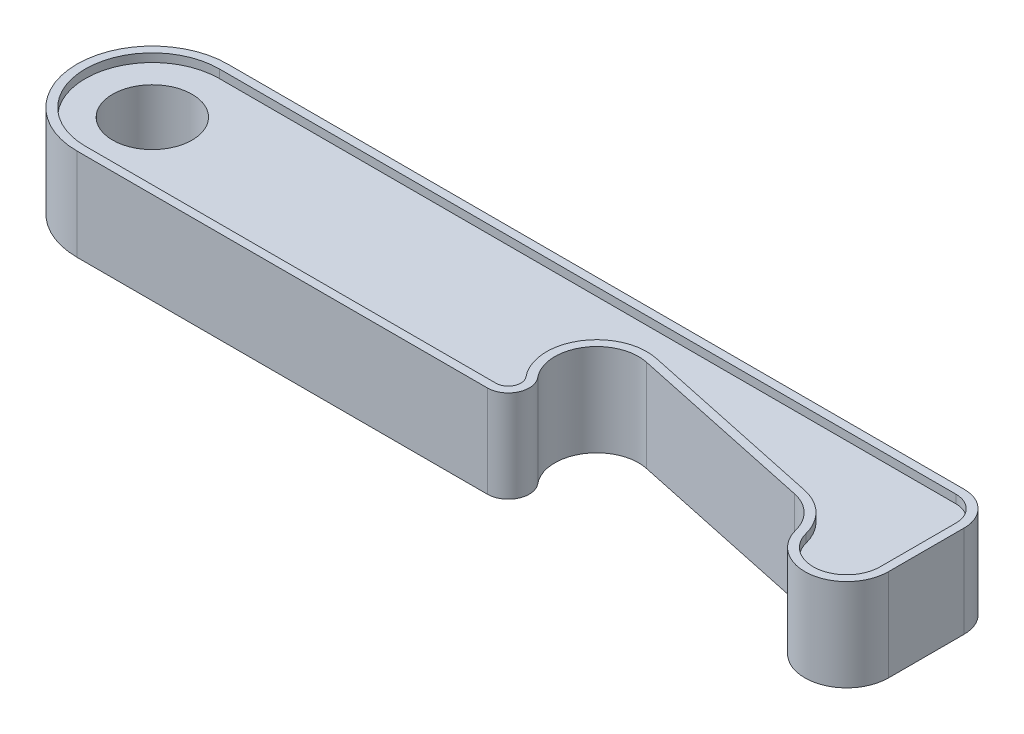
SolidWorks part; units mm, degrees
ref_plane "Front Plane" through (0, 0, 0) normal (0, 0, 1) x (1, 0, 0)
ref_plane "Top Plane" through (0, 0, 0) normal (0, 1, 0) x (1, 0, 0)
ref_plane "Right Plane" through (0, 0, 0) normal (1, 0, 0) x (0, 0, -1)
sketch "Sketch2" plane through (0, 0, 0) normal (0, 1, 0) x (1, 0, 0)
  line L0 (0, 9) -> (88, 9)
  line L1 (92, 5) -> (92, -4.0386)
  line L2 (78.3472, -1.6093) -> (55.8472, 3.1733)
  line L3 (0, -9) -> (49.0303, -9)
  line L4 (0, 8) -> (88, 8)
  line L5 (91, 5) -> (91, -4.0386)
  line L6 (78.5551, -0.6311) -> (56.0551, 4.1514)
  line L7 (0, -8) -> (49.0303, -8)
  circle A0 centre (0, 0) radius 4.75
  arc A1 (0, 9) -> (0, -9) centre (0, 0) ccw
  arc A2 (88, 9) -> (92, 5) centre (88, 5) cw
  arc A3 (92, -4.0386) -> (82.1538, -5.2693) centre (87, -4.0386) cw
  arc A4 (55.8472, 3.1733) -> (50.9561, -4.9058) centre (54.8077, -1.7175) ccw
  arc A5 (78.3472, -1.6093) -> (82.1538, -5.2693) centre (77.3077, -6.5) cw
  arc A6 (49.0303, -9) -> (50.9561, -4.9058) centre (49.0303, -6.5) ccw
  arc A7 (88, 8) -> (91, 5) centre (88, 5) cw
  arc A8 (91, -4.0386) -> (83.1231, -5.0232) centre (87, -4.0386) cw
  arc A9 (78.5551, -0.6311) -> (83.1231, -5.0232) centre (77.3077, -6.5) cw
  arc A10 (56.0551, 4.1514) -> (50.1858, -5.5435) centre (54.8077, -1.7175) ccw
  arc A11 (49.0303, -8) -> (50.1858, -5.5435) centre (49.0303, -6.5) ccw
  arc A12 (0, 8) -> (0, -8) centre (0, 0) ccw
  point P16 (-9, 0)
  point P17 (92, 0.4807)
  point P18 (0, 0)
  point P19 (87.6201, -9)
  point P20 (0, 0)
  point P23 (0, 0)
  point P24 (0, 0)
  point P25 (0, 0)
  dimension "D1" = 9.5
  dimension "D2" = 18
  dimension "D4" = 5
  dimension "D5" = 5
  dimension "D6" = 4
  dimension "D7" = 5
  dimension "D11" = 2.5
  dimension "D3" = 12
  dimension "D8" = 22.5
  dimension "D9" = 101
  dimension "D10" = 18
  dimension "D12" = 18
  dimension "D13" = 1
extrude "Boss-Extrude1" add sketch "Sketch2" along normal mid plane 11 contours A12 L7 A11 A10 L6 A9 A8 L5 A7 L4 | A1 L3 A6 A4 L2 A5 A3 L1 A2 L0
extrude "Boss-Extrude2" add sketch "Sketch2<3>" along normal mid plane 9 contours L4 A12 L7 A11 A10 L6 A9 A8 L5 A7 A0 region at (38.4445, 0, -0.8524)
sketch "Sketch2<3>" plane through (0, 0, 0) normal (0, 1, 0) x (1, 0, 0) same geometry as "Sketch2"
